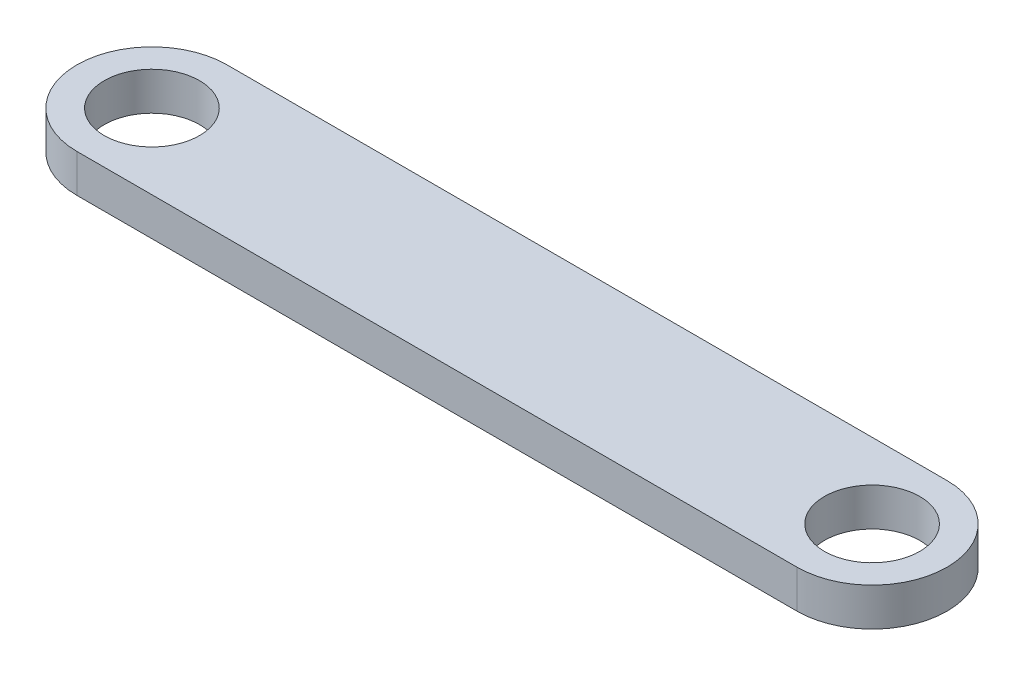
SolidWorks part; units mm, degrees
ref_plane "Front Plane" through (0, 0, 0) normal (0, 0, 1) x (1, 0, 0)
ref_plane "Top Plane" through (0, 0, 0) normal (0, 1, 0) x (1, 0, 0)
ref_plane "Right Plane" through (0, 0, 0) normal (1, 0, 0) x (0, 0, -1)
sketch "Sketch1" plane through (0, 0, 0) normal (0, 1, 0) x (1, 0, 0)
  line L0 (-30, 0) -> (30, 0) construction
  line L1 (-30, 6.25) -> (30, 6.25)
  line L2 (-30, -6.25) -> (30, -6.25)
  arc A0 (-30, 6.25) -> (-30, -6.25) centre (-30, 0) ccw
  arc A1 (30, -6.25) -> (30, 6.25) centre (30, 0) ccw
  circle A2 centre (-30, 0) radius 3.9688
  circle A3 centre (30, 0) radius 3.9687
  point P2 (0, 0)
  dimension "D3" = 7.9375
  dimension "D1" = 12.5
  dimension "D2" = 60
extrude "Boss-Extrude1" add sketch "Sketch1" along normal blind 3.175
